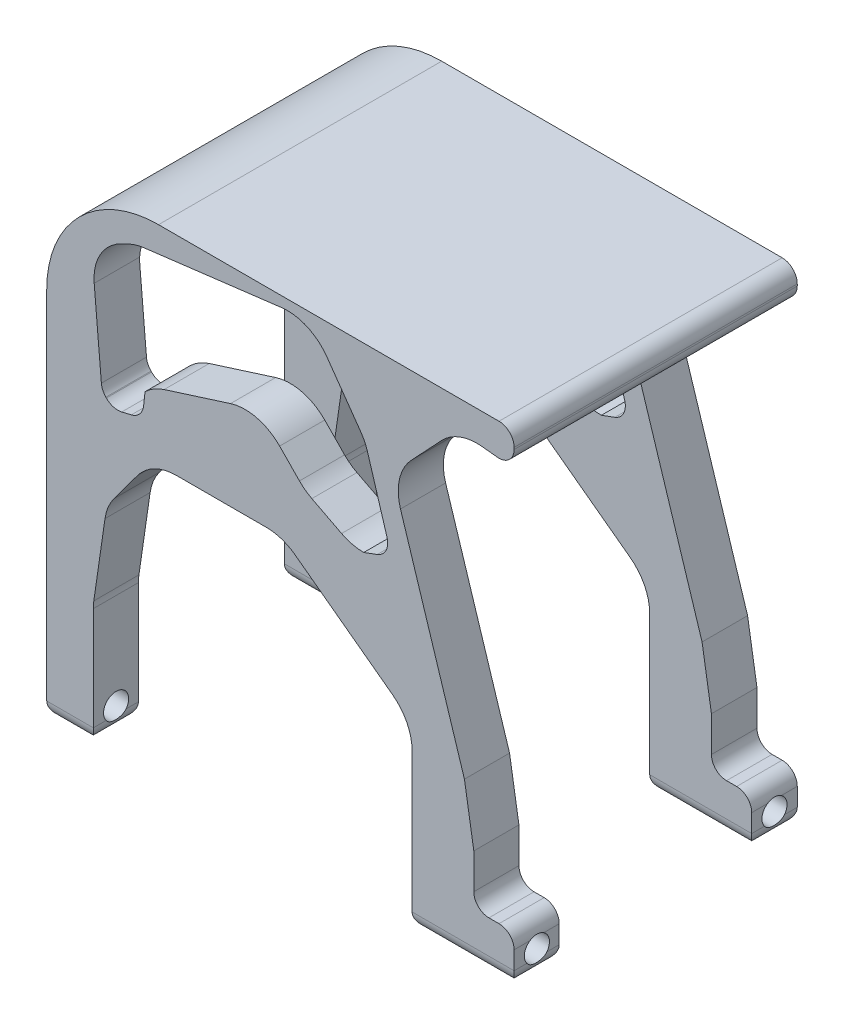
SolidWorks part; units mm, degrees
ref_plane "Front Plane" through (0, 0, 0) normal (0, 0, 1) x (1, 0, 0)
ref_plane "Top Plane" through (0, 0, 0) normal (0, 1, 0) x (1, 0, 0)
ref_plane "Right Plane" through (0, 0, 0) normal (1, 0, 0) x (0, 0, -1)
sketch "Sketch1" plane through (0, 0, 0) normal (0, 0, 1) x (1, 0, 0)
  line L1 (0, 0) -> (73.66, 0)
  line L2 (0, 0) -> (0, 76.2)
  line L3 (0, 76.2) -> (73.66, 76.2)
  line L4 (73.66, 0) -> (73.66, 76.2)
  dimension "D1" = 73.66
  dimension "D2" = 76.2
extrude "Boss-Extrude1" add sketch "Sketch1" along normal blind 44.6278
sketch "Sketch2" plane through (73.66, 0, 0) normal (1, 0, 0) x (0, 0, -1)
  line L0 (-44.6278, 0) -> (0, 0) construction
  line L1 (-37.5158, 0) -> (-7.1755, 0)
  line L2 (-37.5158, 0) -> (-37.5158, 62.23)
  line L3 (-29.8958, 69.85) -> (-14.7955, 69.85)
  line L4 (-7.1755, 0) -> (-7.1755, 62.23)
  line L5 (-44.6278, 0) -> (-44.6278, 76.2) construction
  arc A0 (-14.7955, 69.85) -> (-7.1755, 62.23) centre (-14.7955, 62.23) cw
  arc A1 (-37.5158, 62.23) -> (-29.8958, 69.85) centre (-29.8958, 62.23) cw
  point P12 (-7.1755, 69.85)
  dimension "D4" = 7.62
  dimension "D1" = 30.3403
  dimension "D2" = 69.85
  dimension "D3" = 7.112
extrude "Cut-Extrude1" cut sketch "Sketch2" against normal through all
sketch "Sketch3" plane through (0, 0, 44.6278) normal (0, 0, 1) x (1, 0, 0)
  line L0 (7.3406, 0) -> (7.3406, 41.4646) construction
  line L1 (0, 0) -> (73.66, 0) construction
  line L2 (57.5818, 0) -> (57.5818, 39.3354) construction
  line L3 (0, 76.2) -> (0, 0) construction
  line L4 (20.4271, 43.3819) -> (34.6128, 43.3819)
  line L5 (39.1531, 41.8815) -> (54.5022, 30.4935)
  line L6 (7.3406, 0) -> (7.3406, 18.6502)
  line L7 (7.4198, 19.7462) -> (9.1812, 31.864)
  line L8 (10.6023, 35.3083) -> (14.3075, 40.3022)
  line L9 (57.5818, 24.3739) -> (57.5818, 0)
  line L10 (57.5818, 0) -> (7.3406, 0)
  arc A0 (54.5022, 30.4935) -> (57.5818, 24.3739) centre (49.9618, 24.3739) cw
  arc A1 (34.6128, 43.3819) -> (39.1531, 41.8815) centre (34.6128, 35.7619) cw
  arc A2 (14.3075, 40.3022) -> (20.4271, 43.3819) centre (20.4271, 35.7619) cw
  arc A3 (9.1812, 31.864) -> (10.6023, 35.3083) centre (16.722, 30.7679) cw
  arc A4 (7.3406, 18.6502) -> (7.4198, 19.7462) centre (14.9606, 18.6502) cw
  point P15 (57.5818, 28.2086)
  point P24 (7.3406, 19.2011)
  dimension "D3" = 7.62
  dimension "D1" = 7.3406
  dimension "D2" = 50.2412
extrude "Cut-Extrude2" cut sketch "Sketch3" against normal blind 46.4439
fillet "Fillet4" radius 2.38 16 edges at (65.6209, 0, 7.1755) (57.5818, 0, 3.5877) (65.6209, 0, 0) (73.66, 0, 3.5878) (7.3406, 0, 3.5877) (3.6703, 0, 7.1755) (3.6703, 0, 0) (0, 0, 3.5877) (0, 0, 41.0718) (57.5818, 0, 41.0718) (3.6703, 0, 37.5158) (7.3406, 0, 41.0718) (3.6703, 0, 44.6278) (65.6209, 0, 37.5158) (73.66, 0, 41.0718) (65.6209, 0, 44.6278)
sketch "Sketch4" plane through (0, 0, 0) normal (-1, 0, 0) x (0, 0, 1)
  line L0 (-1.4585, 1.6002) -> (12.0714, 1.6002) construction
  line L1 (0, 76.2) -> (0, 2.38) construction
  circle A0 centre (3.5898, 3.5814) radius 1.9812
  point P4 (3.5898, 1.6002)
  point P6 (0, 0)
  dimension "D1" = 3.9624
  dimension "D2" = 1.6002
  dimension "D3" = 3.5898
extrude "Cut-Extrude3" cut sketch "Sketch4" against normal blind 110.4519
ref_plane "Plane1" through (0, 0, 22.3139) normal (0, 0, -1) x (-1, 0, 0)
mirror "Mirror1" about plane through (0, 0, 22.3139) normal (0, 0, -1) of "Cut-Extrude3"
sketch "Sketch5" plane through (0, 0, 0) normal (0, 0, -1) x (-1, 0, 0)
  line L0 (-73.66, 7.62) -> (-67.31, 7.62)
  line L1 (-73.66, 2.38) -> (-73.66, 76.2) construction
  line L2 (-67.31, 7.62) -> (-67.31, 15.567)
  line L3 (-67.31, 15.567) -> (-65.8315, 24.6228)
  line L4 (-65.8315, 24.6228) -> (-55.7534, 56.4569)
  line L5 (-57.4675, 63.9775) -> (-62.2441, 69.0559)
  line L6 (-68.5787, 71.4147) -> (-73.66, 70.889)
  line L7 (-73.66, 70.889) -> (-73.66, 7.62)
  line L8 (-15.2709, 71.8931) -> (-37.0088, 74.5755)
  line L9 (-44.1673, 71.4071) -> (-49.4813, 63.8788)
  line L12 (-28.962, 57.4496) -> (-18.5041, 54.1388)
  line L15 (-11.7606, 70.6477) -> (-12.8959, 71.1949)
  line L17 (-46.4676, 48.4733) -> (-41.7808, 50.8901)
  line L18 (-39.8321, 52.328) -> (-36.703, 55.5196)
  line L19 (-50.5206, 61.7844) -> (-53.6334, 51.5339)
  line L20 (-52.0862, 48.4144) -> (-49.96, 47.6258)
  line L21 (-7.4772, 63.1253) -> (-8.6094, 50.0634)
  line L22 (-9.3192, 48.5116) -> (-9.4002, 48.4283)
  line L24 (-15.4906, 52.328) -> (-15.4906, 52.3361)
  line L25 (-15.4906, 52.328) -> (-15.2648, 50.2854)
  line L26 (-13.3335, 48.0947) -> (-11.8142, 47.7297)
  line L27 (-59.9618, 0) -> (-71.28, 0) construction
  arc A0 (-49.96, 47.6258) -> (-46.4676, 48.4733) centre (-49.96, 55.2458) ccw
  arc A1 (-41.7808, 50.8901) -> (-39.8321, 52.328) centre (-45.2732, 57.6627) ccw
  arc A2 (-36.703, 55.5196) -> (-28.962, 57.4496) centre (-31.2619, 50.185) cw
  arc A3 (-18.5041, 54.1388) -> (-15.4906, 52.3361) centre (-20.804, 46.8742) cw
  arc A4 (-7.4772, 63.1253) -> (-11.7606, 70.6477) centre (-15.0688, 63.7833) ccw
  arc A5 (-15.2709, 71.8931) -> (-12.8959, 71.1949) centre (-16.2041, 64.3305) cw
  arc A6 (-37.0088, 74.5755) -> (-44.1673, 71.4071) centre (-37.942, 67.0129) ccw
  arc A7 (-49.4813, 63.8788) -> (-50.5206, 61.7844) centre (-43.256, 59.4846) ccw
  arc A8 (-55.7534, 56.4569) -> (-57.4675, 63.9775) centre (-63.018, 58.7568) ccw
  arc A9 (-62.2441, 69.0559) -> (-68.5787, 71.4147) centre (-67.7946, 63.8351) ccw
  arc A10 (-8.6094, 50.0634) -> (-9.3192, 48.5116) centre (-11.1399, 50.2827) cw
  arc A11 (-53.6334, 51.5339) -> (-52.0862, 48.4144) centre (-51.203, 50.7959) ccw
  arc A12 (-9.4002, 48.4283) -> (-11.8142, 47.7297) centre (-11.2209, 50.1995) cw
  arc A13 (-15.2648, 50.2854) -> (-13.3335, 48.0947) centre (-12.7402, 50.5645) ccw
  dimension "D1" = 7.62
  dimension "D2" = 2.54
  dimension "D3" = 2.54
  dimension "D4" = 6.35
  dimension "D5" = 7.62
extrude "Cut-Extrude4" cut sketch "Sketch5" against normal blind 110.4519
fillet "Fillet5" radius 17.62 1 edges at (0, 76.2, 22.3139)
fillet "Fillet6" radius 2.38 1 edges at (73.66, 70.889, 22.3139)
fillet "Fillet7" radius 2.38 4 edges at (73.66, 7.62, 41.0718) (67.31, 7.62, 41.0718) (73.66, 7.62, 3.5878) (67.31, 7.62, 3.5877)
fillet "Fillet8" radius 2.38 1 edges at (73.66, 76.2, 22.3139)
